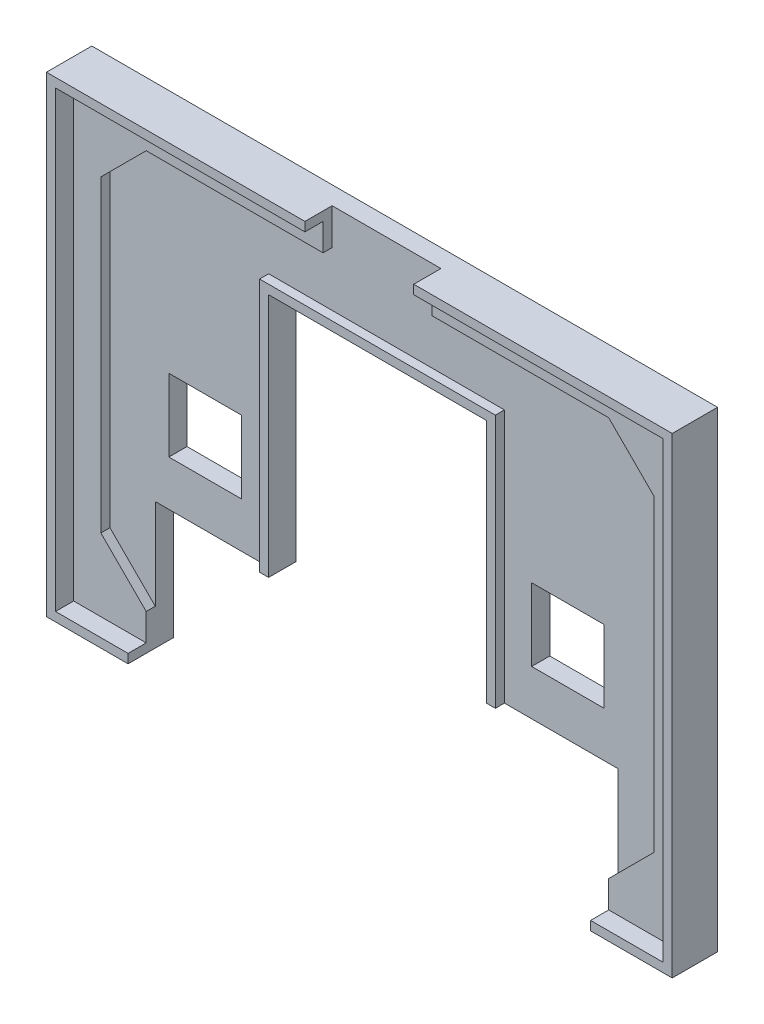
SolidWorks part; units mm, degrees
ref_plane "Přední rovina" through (0, 0, 0) normal (0, 0, 1) x (1, 0, 0)
ref_plane "Horní rovina" through (0, 0, 0) normal (0, 1, 0) x (1, 0, 0)
ref_plane "Pravá rovina" through (0, 0, 0) normal (1, 0, 0) x (0, 0, -1)
sketch "Skica1" plane through (0, 0, 0) normal (0, 0, 1) x (1, 0, 0)
  line L1 (-33.5, -25) -> (33.5, -25)
  line L2 (-33.5, -25) -> (-33.5, 25)
  line L3 (-33.5, 25) -> (33.5, 25)
  line L4 (33.5, -25) -> (33.5, 25)
  line L5 (-33.5, -25) -> (33.5, 25) construction
  line L6 (-33.5, 25) -> (33.5, -25) construction
  point P0 (0, 0)
  dimension "D1" = 67
  dimension "D2" = 50
extrude "Přidat vysunutím1" add sketch "Skica1" along normal blind 3
sketch "Skica2" plane through (0, 0, 3) normal (0, 0, 1) x (1, 0, 0)
  line L0 (-1000, 0) -> (49000, 0) construction
  line L1 (0, -1000) -> (0, 49000) construction
  line L2 (-1000, -22) -> (49000, -22) construction
  line L3 (-25.5, -1000) -> (-25.5, 49000) construction
  line L4 (-30.5, -1000) -> (-30.5, 49000) construction
  line L6 (-33.5, -25) -> (33.5, -25) construction
  line L7 (-25.5, -22) -> (-30.5, -17)
  line L8 (-30.5, -17) -> (-30.5, 17)
  line L9 (-25.5, -22) -> (25.5, -22)
  line L10 (30.5, -17) -> (30.5, 17)
  line L11 (25.5, -22) -> (30.5, -17)
  line L12 (25.5, 22) -> (30.5, 17)
  line L13 (-25.5, 22) -> (25.5, 22)
  line L14 (-25.5, 22) -> (-30.5, 17)
  point P20 (0, -22)
  point P21 (30.5, 0)
  point P24 (-30.5, 0)
  dimension "D1" = 30.5
  dimension "D2" = 5
  dimension "D3" = 3
  dimension "D4" = 45
extrude "Odebrat vysunutím1" cut sketch "Skica2" against normal offset from surface (1 mm away) 2 up to face at (0, 0, 0)
sketch "Skica3" plane through (0, 0, 0) normal (0, 0, -1) x (-1, 0, 0)
  line L0 (0, -1000) -> (0, 49000) construction
  line L1 (33.5, -25) -> (-33.5, -25) construction
  line L2 (24, 1) -> (16, 1)
  line L3 (24, 1) -> (24, -7)
  line L4 (24, -7) -> (16, -7)
  line L5 (16, 1) -> (16, -7)
  line L6 (-16, 1) -> (-16, -7)
  line L7 (33.5, -25) -> (-33.5, -25) construction
  line L8 (25.5, -25) -> (-25.5, -25)
  line L9 (25.5, -25) -> (25.5, -12)
  line L11 (-25.5, -25) -> (-25.5, -12)
  line L12 (-24, -7) -> (-16, -7)
  line L13 (25.5, -12) -> (12, -12)
  line L15 (12, -12) -> (12, 15)
  line L16 (12, 15) -> (-12, 15)
  line L17 (-12, -12) -> (-12, 15)
  line L18 (-12, -12) -> (-25.5, -12)
  line L19 (-24, 1) -> (-24, -7)
  line L20 (-24, 1) -> (-16, 1)
  dimension "D1" = 16
  dimension "D2" = 8
  dimension "D3" = 18
  dimension "D4" = 13
  dimension "D5" = 51
  dimension "D6" = 24
  dimension "D7" = 27
extrude "Odebrat vysunutím2" cut sketch "Skica3" against normal through all
sketch "Skica4" plane through (0, 0, 2) normal (0, 0, 1) x (1, 0, 0)
  line L0 (12, 15) -> (12, -12) construction
  line L1 (-12, -12) -> (-12, 15) construction
  line L2 (-12, 15) -> (12, 15) construction
  line L3 (12, 15) -> (12, -12)
  line L4 (-12, -12) -> (-12, 15)
  line L5 (-12, 15) -> (12, 15)
extrude "Vysunout tenkostěnný1" add sketch "Skica4" along normal up to surface (1 mm away) thin up to face at (0, -3.5714, 3) thin type one direction reverse wall 1
sketch "Skica5" plane through (0, 0, 0) normal (0, 0, -1) x (-1, 0, 0)
  line L0 (-33.5, 25) -> (33.5, 25) construction
  line L1 (33.5, 25) -> (33.5, -25) construction
  line L2 (33.5, -25) -> (25.5, -25) construction
  line L3 (-33.5, -25) -> (-33.5, 25) construction
  line L4 (-25.5, -25) -> (-33.5, -25) construction
  line L5 (-33.5, 25) -> (33.5, 25)
  line L6 (33.5, 25) -> (33.5, -25)
  line L7 (33.5, -25) -> (25.5, -25)
  line L8 (-33.5, -25) -> (-33.5, 25)
  line L9 (-25.5, -25) -> (-33.5, -25)
extrude "Vysunout tenkostěnný2" add sketch "Skica5" against normal blind 5 thin thin type one direction reverse wall 1
sketch "Skica6" plane through (0, 0, 2) normal (0, 0, 1) x (1, 0, 0)
  line L0 (0, -1000) -> (0, 49000) construction
  line L1 (25.5, 22) -> (-25.5, 22) construction
  line L2 (-6, 22) -> (6, 22)
  line L3 (-6, 22) -> (-6, 26)
  line L4 (-6, 26) -> (6, 26)
  line L5 (6, 22) -> (6, 26)
  line L6 (34.5, 26) -> (-34.5, 26) construction
  dimension "D1" = 12
extrude "Odebrat vysunutím3" cut sketch "Skica6" along normal through all
sketch "Skica7" plane through (0, 0, 0) normal (0, 0, -1) x (-1, 0, 0)
  line L2 (-27.7648, 19.0706) -> (-26.1648, 19.0706)
  line L3 (-26.1648, 19.0706) -> (-26.1648, 17.4706)
  line L4 (-26.1648, 17.4706) -> (-20.2437, 17.4706)
  line L6 (-18.6437, 11.4605) -> (-27.7648, 11.4605)
  line L7 (-27.7648, 11.4605) -> (-27.7648, 9.8605)
  line L8 (-27.7648, 9.8605) -> (-29.3648, 9.8605)
  line L9 (-29.3648, 9.8605) -> (-29.3648, 8.2705)
  line L10 (-29.3648, 8.2705) -> (-30.9648, 8.2705)
  line L11 (-30.9648, 8.2705) -> (-30.9648, 9.8705)
  line L12 (-30.9648, 9.8705) -> (-29.3748, 9.8705)
  line L13 (-29.3748, 9.8705) -> (-29.3748, 12.5751)
  line L14 (-29.3748, 12.5751) -> (-30.9748, 12.5751)
  line L15 (-30.9748, 12.5751) -> (-30.9748, 14.2904)
  line L16 (-30.9748, 14.2904) -> (-32.5748, 14.2904)
  line L17 (-32.5748, 14.2904) -> (-32.5748, 19.0606)
  line L18 (-32.5748, 19.0606) -> (-30.9748, 19.0606)
  line L19 (-30.9748, 19.0606) -> (-30.9748, 15.8053)
  line L20 (-30.9748, 15.8053) -> (-29.3748, 15.8053)
  line L21 (-29.3748, 15.8053) -> (-29.3748, 17.433)
  line L22 (-29.3748, 17.433) -> (-27.7748, 17.433)
  line L23 (-27.7748, 17.433) -> (-27.7748, 19.0606)
  line L24 (-27.7748, 19.0606) -> (-29.3648, 19.0606)
  line L27 (-29.3648, 19.0606) -> (-29.3648, 20.747)
  line L28 (-29.3648, 20.747) -> (-27.7648, 20.747)
  line L29 (-27.7648, 20.747) -> (-27.7648, 19.0706)
  line L30 (-34.5, -26) -> (-34.5, 26) construction
  line L31 (-17.0437, 20.747) -> (-18.6437, 20.747)
  line L32 (-17.0437, 19.0606) -> (-17.0437, 20.747)
  line L33 (-18.6337, 19.0606) -> (-17.0437, 19.0606)
  line L34 (-18.6337, 17.433) -> (-18.6337, 19.0606)
  line L35 (-17.0337, 17.433) -> (-18.6337, 17.433)
  line L36 (-17.0337, 15.8053) -> (-17.0337, 17.433)
  line L37 (-15.4337, 15.8053) -> (-17.0337, 15.8053)
  line L38 (-15.4337, 19.0606) -> (-15.4337, 15.8053)
  line L39 (-13.8337, 19.0606) -> (-15.4337, 19.0606)
  line L40 (-13.8337, 14.2904) -> (-13.8337, 19.0606)
  line L41 (-15.4337, 14.2904) -> (-13.8337, 14.2904)
  line L42 (-15.4337, 12.5751) -> (-15.4337, 14.2904)
  line L43 (-17.0337, 12.5751) -> (-15.4337, 12.5751)
  line L44 (-17.0337, 9.8705) -> (-17.0337, 12.5751)
  line L45 (-15.4437, 9.8705) -> (-17.0337, 9.8705)
  line L46 (-15.4437, 8.2705) -> (-15.4437, 9.8705)
  line L47 (-17.0437, 8.2705) -> (-15.4437, 8.2705)
  line L48 (-17.0437, 9.8605) -> (-17.0437, 8.2705)
  line L49 (-18.6437, 9.8605) -> (-17.0437, 9.8605)
  line L50 (-18.6437, 11.4605) -> (-18.6437, 9.8605)
  line L51 (-20.2437, 19.0706) -> (-20.2437, 17.4706)
  line L52 (-18.6437, 19.0706) -> (-20.2437, 19.0706)
  line L53 (-18.6437, 20.747) -> (-18.6437, 19.0706)
  line L54 (34.5, 26) -> (34.5, -26) construction
  line L103 (-25.5, -26) -> (-34.5, -26) construction
  line L104 (34.5, -26) -> (25.5, -26) construction
  line L105 (0, 0) -> (0, 33.5419) construction
  line L106 (17.0437, 19.0606) -> (17.0437, 20.747)
  line L107 (18.6337, 19.0606) -> (17.0437, 19.0606)
  line L108 (18.6337, 17.433) -> (18.6337, 19.0606)
  line L109 (17.0337, 17.433) -> (18.6337, 17.433)
  line L110 (17.0337, 15.8053) -> (17.0337, 17.433)
  line L111 (15.4337, 15.8053) -> (17.0337, 15.8053)
  line L112 (15.4337, 19.0606) -> (15.4337, 15.8053)
  line L113 (13.8337, 19.0606) -> (15.4337, 19.0606)
  line L114 (13.8337, 14.2904) -> (13.8337, 19.0606)
  line L115 (15.4337, 14.2904) -> (13.8337, 14.2904)
  line L116 (15.4337, 12.5751) -> (15.4337, 14.2904)
  line L117 (17.0337, 12.5751) -> (15.4337, 12.5751)
  line L118 (17.0337, 9.8705) -> (17.0337, 12.5751)
  line L119 (15.4437, 9.8705) -> (17.0337, 9.8705)
  line L120 (15.4437, 8.2705) -> (15.4437, 9.8705)
  line L121 (17.0437, 8.2705) -> (15.4437, 8.2705)
  line L122 (17.0437, 9.8605) -> (17.0437, 8.2705)
  line L123 (18.6437, 9.8605) -> (17.0437, 9.8605)
  line L124 (18.6437, 11.4605) -> (18.6437, 9.8605)
  line L125 (18.6437, 11.4605) -> (27.7648, 11.4605)
  line L126 (27.7648, 11.4605) -> (27.7648, 9.8605)
  line L127 (27.7648, 9.8605) -> (29.3648, 9.8605)
  line L128 (29.3648, 9.8605) -> (29.3648, 8.2705)
  line L129 (29.3648, 8.2705) -> (30.9648, 8.2705)
  line L130 (30.9648, 8.2705) -> (30.9648, 9.8705)
  line L131 (30.9648, 9.8705) -> (29.3748, 9.8705)
  line L132 (29.3748, 9.8705) -> (29.3748, 12.5751)
  line L133 (29.3748, 12.5751) -> (30.9748, 12.5751)
  line L134 (30.9748, 12.5751) -> (30.9748, 14.2904)
  line L135 (30.9748, 14.2904) -> (32.5748, 14.2904)
  line L136 (32.5748, 14.2904) -> (32.5748, 19.0606)
  line L137 (32.5748, 19.0606) -> (30.9748, 19.0606)
  line L138 (30.9748, 19.0606) -> (30.9748, 15.8053)
  line L139 (30.9748, 15.8053) -> (29.3748, 15.8053)
  line L140 (29.3748, 15.8053) -> (29.3748, 17.433)
  line L141 (29.3748, 17.433) -> (27.7748, 17.433)
  line L142 (27.7748, 17.433) -> (27.7748, 19.0606)
  line L143 (27.7748, 19.0606) -> (29.3648, 19.0606)
  line L144 (29.3648, 19.0606) -> (29.3648, 20.747)
  line L145 (29.3648, 20.747) -> (27.7648, 20.747)
  line L146 (27.7648, 20.747) -> (27.7648, 19.0706)
  line L147 (27.7648, 19.0706) -> (26.1648, 19.0706)
  line L148 (26.1648, 19.0706) -> (26.1648, 17.4706)
  line L149 (26.1648, 17.4706) -> (20.2437, 17.4706)
  line L150 (20.2437, 19.0706) -> (20.2437, 17.4706)
  line L151 (18.6437, 19.0706) -> (20.2437, 19.0706)
  line L152 (18.6437, 20.747) -> (18.6437, 19.0706)
  line L153 (17.0437, 20.747) -> (18.6437, 20.747)
  dimension "D1" = 1.9252
  dimension "D2" = 3.5252
  dimension "D3" = 3.5352
  dimension "D4" = 14.2563
  dimension "D5" = 34.2705
  dimension "D6" = 38.5751
  dimension "D7" = 40.2904
  dimension "D8" = 41.8053
  dimension "D9" = 43.433
  dimension "D10" = 43.4706
  dimension "D11" = 46.747
extrude "Odebrat vysunutím5" cut sketch "Skica7" against normal blind 1
sketch "Skica8" plane through (0, 0, 1) normal (0, 0, -1) x (-1, 0, 0)
  line L1 (-26.1648, 15.8053) -> (-24.5648, 15.8053)
  line L2 (-26.1648, 15.8053) -> (-26.1648, 14.2053)
  line L3 (-26.1648, 14.2053) -> (-24.5648, 14.2053)
  line L4 (-24.5648, 15.8053) -> (-24.5648, 14.2053)
  line L6 (-23.2043, 11.4605) -> (-23.2043, 22.3492) construction
  line L7 (-27.7648, 11.4605) -> (-18.6437, 11.4605) construction
  line L8 (-20.2437, 14.2053) -> (-21.8437, 14.2053)
  line L9 (-21.8437, 15.8053) -> (-21.8437, 14.2053)
  line L10 (-20.2437, 15.8053) -> (-21.8437, 15.8053)
  line L11 (-20.2437, 15.8053) -> (-20.2437, 14.2053)
  line L12 (0, 0) -> (0, 33.6898) construction
  line L13 (-17.0437, 9.8605) -> (-17.0437, 8.2705) construction
  line L14 (-30.9648, 8.2705) -> (-29.3648, 8.2705) construction
  line L15 (20.2437, 15.8053) -> (20.2437, 14.2053)
  line L16 (20.2437, 15.8053) -> (21.8437, 15.8053)
  line L17 (21.8437, 15.8053) -> (21.8437, 14.2053)
  line L18 (20.2437, 14.2053) -> (21.8437, 14.2053)
  line L19 (26.1648, 14.2053) -> (24.5648, 14.2053)
  line L20 (24.5648, 15.8053) -> (24.5648, 14.2053)
  line L21 (26.1648, 15.8053) -> (24.5648, 15.8053)
  line L22 (26.1648, 15.8053) -> (26.1648, 14.2053)
  dimension "D1" = 3.2
  dimension "D2" = 4.8
  dimension "D3" = 5.9348
extrude "Přidat vysunutím2" add sketch "Skica8" along normal blind 1
sketch "Skica9" plane through (0, 0, 0) normal (0, 0, -1) x (-1, 0, 0)
  line L0 (-32.5748, 19.0606) -> (-32.5748, 14.2904) construction
  line L1 (-30.9648, 8.2705) -> (-29.3648, 8.2705) construction
  text T0 "XENO" font "BLOXAT" height 5.7
  dimension "D1" = 21.2712
  dimension "D2" = 9.3407
extrude "Odebrat vysunutím6" cut sketch "Skica9" against normal blind 1
